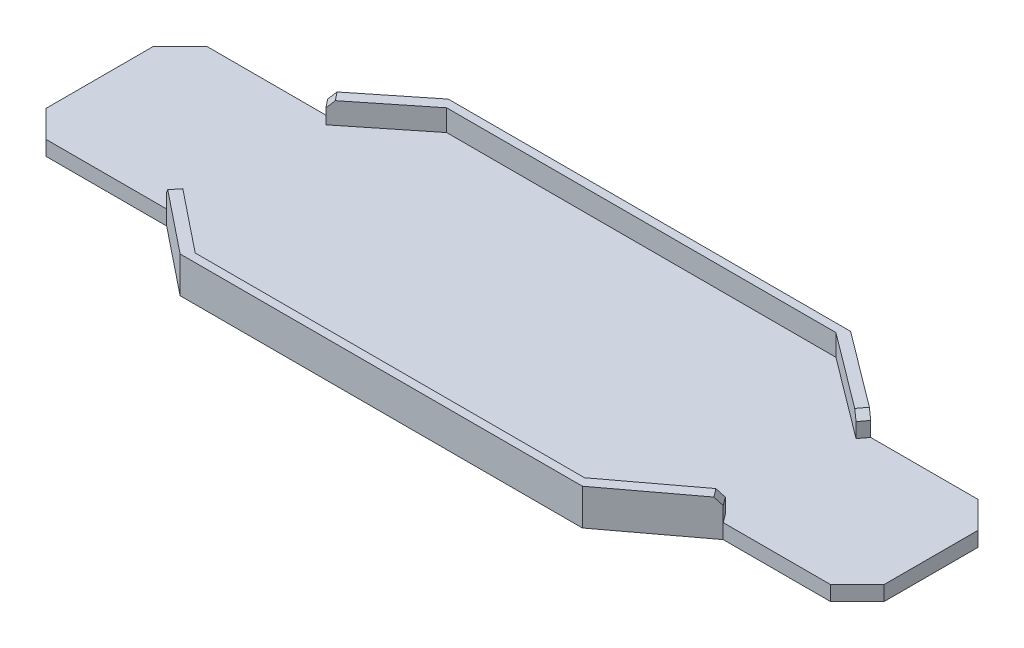
SolidWorks part; units mm, degrees
ref_plane "Front Plane" through (0, 0, 0) normal (0, 0, 1) x (1, 0, 0)
ref_plane "Top Plane" through (0, 0, 0) normal (0, 1, 0) x (1, 0, 0)
ref_plane "Right Plane" through (0, 0, 0) normal (1, 0, 0) x (0, 0, -1)
sketch "Sketch1" plane through (0, 0, 0) normal (0, 1, 0) x (1, 0, 0)
  line L0 (-235.1499, 0) -> (235.1499, 0) construction
  line L1 (0, 0) -> (0, 52596.8311) construction
  line L2 (-100, 30) -> (-75, 50)
  line L3 (-75, 50) -> (75, 50)
  line L4 (-100, 30) -> (-155, 30)
  line L5 (-155, 30) -> (-155, -30)
  line L6 (-75, -50) -> (75, -50)
  line L7 (-100, -30) -> (-75, -50)
  line L8 (-100, -30) -> (-155, -30)
  line L9 (75, 50) -> (105, 27.5)
  line L10 (105, 27.5) -> (155, 27.5)
  line L11 (155, 27.5) -> (155, -27.5)
  line L12 (105, -27.5) -> (155, -27.5)
  line L13 (75, -50) -> (105, -27.5)
  point P3 (0, 0)
  point P10 (-87.5, 40)
  point P15 (-87.5, -40)
  point P18 (-155, 0)
  point P19 (0, -50)
  point P20 (0, 50)
  point P23 (155, 0)
  dimension "D1" = 50
  dimension "D2" = 60
  dimension "D3" = 25
  dimension "D4" = 55
  dimension "D5" = 150
  dimension "D6" = 50
  dimension "D7" = 55
  dimension "D8" = 30
extrude "Boss-Extrude1" add sketch "Sketch1" along normal blind 5.5
sketch "Sketch3" plane through (0, 5.5, 0) normal (0, 1, 0) x (1, 0, 0)
  line L0 (0, 0) -> (50000, 0) construction
  line L1 (0, 0) -> (0, 50000) construction
  line L2 (0, 50) -> (-75, 50)
  line L3 (75, 50) -> (-75, 50) construction
  line L4 (-75, 50) -> (-100, 30)
  line L5 (-100, 30) -> (-97.5012, 26.8765)
  line L6 (-97.5012, 26.8765) -> (-72.5012, 46.8765)
  line L7 (-72.5012, 46.8765) -> (0, 46.8765)
  line L8 (-75, 50) -> (-72.5012, 46.8765) construction
  line L9 (0, 50) -> (75, 50)
  line L10 (75, 50) -> (105, 27.5)
  line L11 (105, 27.5) -> (102.6574, 24.3765)
  line L12 (102.6574, 24.3765) -> (72.6574, 46.8765)
  line L13 (72.6574, 46.8765) -> (0, 46.8765)
  line L14 (72.6574, 46.8765) -> (75, 50) construction
  line L15 (72.6574, -46.8765) -> (75, -50) construction
  line L16 (-75, -50) -> (-72.5012, -46.8765) construction
  line L17 (72.6574, -46.8765) -> (0, -46.8765)
  line L18 (102.6574, -24.3765) -> (72.6574, -46.8765)
  line L19 (105, -27.5) -> (102.6574, -24.3765)
  line L20 (75, -50) -> (105, -27.5)
  line L21 (0, -50) -> (75, -50)
  line L22 (-72.5012, -46.8765) -> (0, -46.8765)
  line L23 (-97.5012, -26.8765) -> (-72.5012, -46.8765)
  line L24 (-100, -30) -> (-97.5012, -26.8765)
  line L25 (-75, -50) -> (-100, -30)
  line L26 (0, -50) -> (-75, -50)
  dimension "D1" = 4
extrude "Chassis-Walls1" add sketch "Sketch3" along normal blind 8
chamfer "Chamfer1" distance 10 angle 45 2 edges at (-155, 2.75, -30) (-155, 2.75, 30)
chamfer "Chamfer2" distance 10 angle 45 2 edges at (155, 2.75, -27.5) (155, 2.75, 27.5)
chamfer "Chamfer3" distance 2.5 angle 45 4 edges at (-98.7506, 13.5, -28.4383) (-98.7506, 13.5, 28.4383) (103.8287, 13.5, 25.9383) (103.8287, 13.5, -25.9383)
